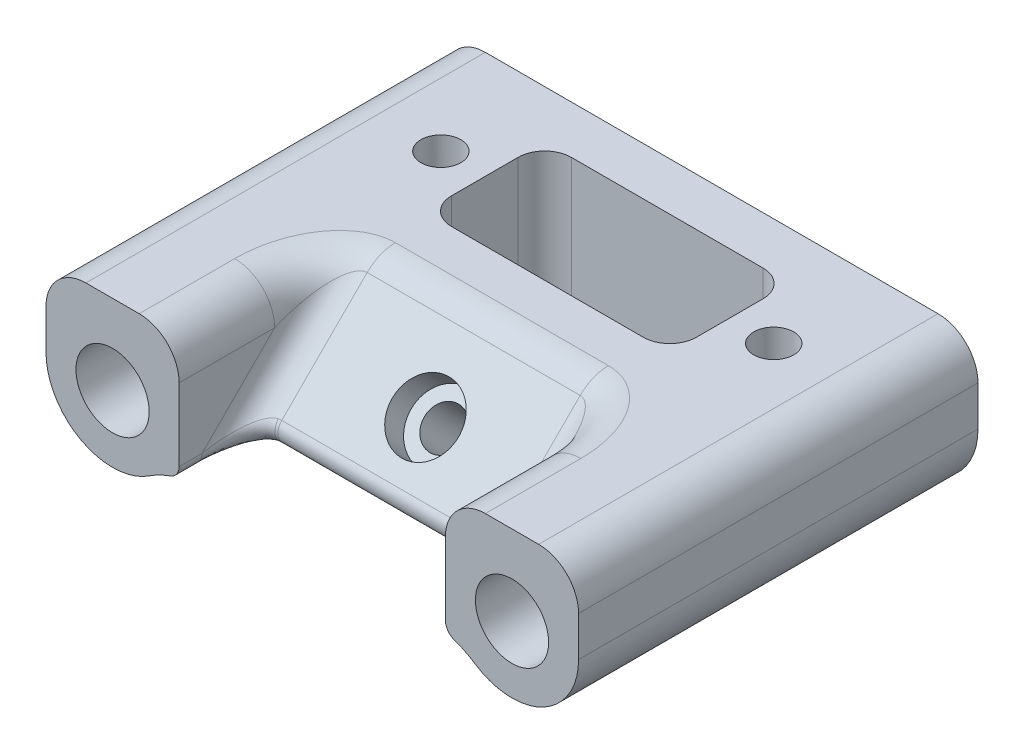
SolidWorks part; units mm, degrees
ref_plane "Front Plane" through (0, 0, 0) normal (0, 0, 1) x (1, 0, 0)
ref_plane "Top Plane" through (0, 0, 0) normal (0, 1, 0) x (1, 0, 0)
ref_plane "Right Plane" through (0, 0, 0) normal (1, 0, 0) x (0, 0, -1)
sketch "Sketch2" plane through (0, 0, 0) normal (0, 0, 1) x (1, 0, 0)
  line L0 (20, 37) -> (20, 40)
  line L2 (17, 43) -> (-17, 43)
  line L3 (-20, 40) -> (-20, 37)
  line L5 (8.3668, 34) -> (-8.3668, 34)
  circle A1 centre (15, 37) radius 2.75
  circle A3 centre (-15, 37) radius 2.75
  arc A4 (-20, 37) -> (-12.2361, 32.8333) centre (-15, 37) ccw
  arc A5 (12.2361, 32.8333) -> (20, 37) centre (15, 37) ccw
  arc A6 (20, 40) -> (17, 43) centre (17, 40) ccw
  arc A7 (-17, 43) -> (-20, 40) centre (-17, 40) ccw
  arc A8 (-8.3668, 34) -> (-12.2361, 32.8333) centre (-8.3668, 27) ccw
  arc A9 (8.3668, 34) -> (12.2361, 32.8333) centre (8.3668, 27) cw
  dimension "D1" = 7
  dimension "D2" = 9
extrude "Boss-Extrude1" add sketch "Sketch2" along normal up to surface (35 mm away)
sketch "Sketch4" plane through (0, 0, 0) normal (1, 0, 0) x (0, 0, -1)
  line L1 (-35, 43) -> (-17, 43)
  line L2 (-35, 43) -> (-35, 32)
  line L3 (-35, 32) -> (-28, 32)
  line L5 (-17, 43) -> (-28, 32)
extrude "Cut-Extrude2" cut sketch "Sketch4" against normal mid plane 20
sketch "Sketch5" plane through (0, 43, 0) normal (0, 1, 0) x (1, 0, 0)
  line L0 (8.2585, -9.6015) -> (8.2585, -6.6015) construction
  line L1 (7.4585, -12.6015) -> (-6.9415, -12.6015)
  line L2 (9.4585, -10.6015) -> (9.4585, -5.6015)
  line L3 (7.4585, -3.6015) -> (-6.9415, -3.6015)
  line L4 (-8.9415, -10.6015) -> (-8.9415, -5.6015)
  line L5 (-7.7415, -6.6015) -> (-7.7415, -9.6015) construction
  line L6 (-5.7415, -11.6015) -> (6.2585, -11.6015) construction
  line L7 (6.2585, -4.6015) -> (-5.7415, -4.6015) construction
  arc A0 (-6.9415, -12.6015) -> (-8.9415, -10.6015) centre (-6.9415, -10.6015) cw
  arc A1 (-6.9415, -3.6015) -> (-8.9415, -5.6015) centre (-6.9415, -5.6015) ccw
  arc A2 (9.4585, -5.6015) -> (7.4585, -3.6015) centre (7.4585, -5.6015) ccw
  arc A3 (7.4585, -12.6015) -> (9.4585, -10.6015) centre (7.4585, -10.6015) ccw
  dimension "D5" = 2
  dimension "D1" = 1.2
  dimension "D2" = 1.2
  dimension "D3" = 1
  dimension "D4" = 1
extrude "Cut-Extrude3" cut sketch "Sketch5" against normal through all
fillet "Fillet1" radius 2 2 edges at (-10, 38.4034, 21.5966) (10, 38.4034, 21.5966)
sketch "Sketch6" plane through (0, 43, 0) normal (0, 1, 0) x (1, 0, 0)
  circle A0 centre (12.7585, -8.1015) radius 1.5
  circle A1 centre (-12.2415, -8.1015) radius 1.5
extrude "Cut-Extrude4" cut sketch "Sketch6" against normal blind 5
sketch "Sketch7" plane through (0, 30, 30) normal (0, 0.7071, 0.7071) x (1, 0, 0)
  line L0 (0, 5.6569) -> (0, 18.3848) construction
  line L1 (8, 5.6569) -> (-8, 5.6569) construction
  line L2 (-8, 18.3848) -> (8, 18.3848) construction
  circle A0 centre (0, 12.0208) radius 2.5
extrude "Cut-Extrude5" cut sketch "Sketch7" against normal blind 2
sketch "Sketch8" plane through (0, 28.5858, 28.5858) normal (0, 0.7071, 0.7071) x (1, 0, 0)
  circle A0 centre (0, 12.0208) radius 1.5
extrude "Cut-Extrude6" cut sketch "Sketch8" against normal through all
fillet "Fillet2" radius 3 5 edges at (-10, 43, 27.4142) (-9.4142, 43, 17.8284) (10, 43, 27.4142) (9.4142, 43, 17.8284) (0, 43, 17)
fillet "Fillet3" radius 1 7 edges at (10, 33.8068, 32.0108) (9.3051, 33.9368, 26.7484) (8.1842, 34, 26.012) (-10, 33.8068, 32.0108) (-9.3627, 33.9288, 26.8293) (-8.1842, 34, 26.012) (0, 34, 26)
sketch "Sketch9" plane through (0, 0, 35) normal (0, 0, 1) x (1, 0, 0)
  line L3 (10, 40) -> (10, 34.5542)
  line L4 (20, 37) -> (20, 40)
  line L5 (17, 43) -> (13, 43)
  line L6 (10, 40) -> (10, 34.5542)
  line L7 (20, 37) -> (20, 40)
  line L8 (17, 43) -> (13, 43)
  line L9 (-10, 34.5542) -> (-10, 40)
  line L10 (-13, 43) -> (-17, 43)
  line L11 (-20, 40) -> (-20, 37)
  line L12 (-10, 34.5542) -> (-10, 40)
  line L13 (-13, 43) -> (-17, 43)
  line L14 (-20, 40) -> (-20, 37)
  arc A5 (10, 34.5542) -> (10.6708, 33.6099) centre (11, 34.5542) ccw
  arc A6 (12.2361, 32.8333) -> (10.6708, 33.6099) centre (8.3668, 27) ccw
  arc A7 (12.2361, 32.8333) -> (20, 37) centre (15, 37) ccw
  arc A8 (20, 40) -> (17, 43) centre (17, 40) ccw
  arc A9 (13, 43) -> (10, 40) centre (13, 40) ccw
  arc A10 (10, 34.5542) -> (10.6708, 33.6099) centre (11, 34.5542) ccw
  arc A11 (12.2361, 32.8333) -> (10.6708, 33.6099) centre (8.3668, 27) ccw
  arc A12 (12.2361, 32.8333) -> (20, 37) centre (15, 37) ccw
  arc A13 (20, 40) -> (17, 43) centre (17, 40) ccw
  arc A14 (13, 43) -> (10, 40) centre (13, 40) ccw
  arc A15 (-10.6708, 33.6099) -> (-12.2361, 32.8333) centre (-8.3668, 27) ccw
  arc A16 (-10.6708, 33.6099) -> (-10, 34.5542) centre (-11, 34.5542) ccw
  arc A17 (-10, 40) -> (-13, 43) centre (-13, 40) ccw
  arc A18 (-17, 43) -> (-20, 40) centre (-17, 40) ccw
  arc A19 (-20, 37) -> (-12.2361, 32.8333) centre (-15, 37) ccw
  arc A20 (-10.6708, 33.6099) -> (-12.2361, 32.8333) centre (-8.3668, 27) ccw
  arc A21 (-10.6708, 33.6099) -> (-10, 34.5542) centre (-11, 34.5542) ccw
  arc A22 (-10, 40) -> (-13, 43) centre (-13, 40) ccw
  arc A23 (-17, 43) -> (-20, 40) centre (-17, 40) ccw
  arc A24 (-20, 37) -> (-12.2361, 32.8333) centre (-15, 37) ccw
  dimension "D1" = 0
  dimension "D2" = 0
extrude "Cut-Extrude7" cut sketch "Sketch9" against normal blind 5
